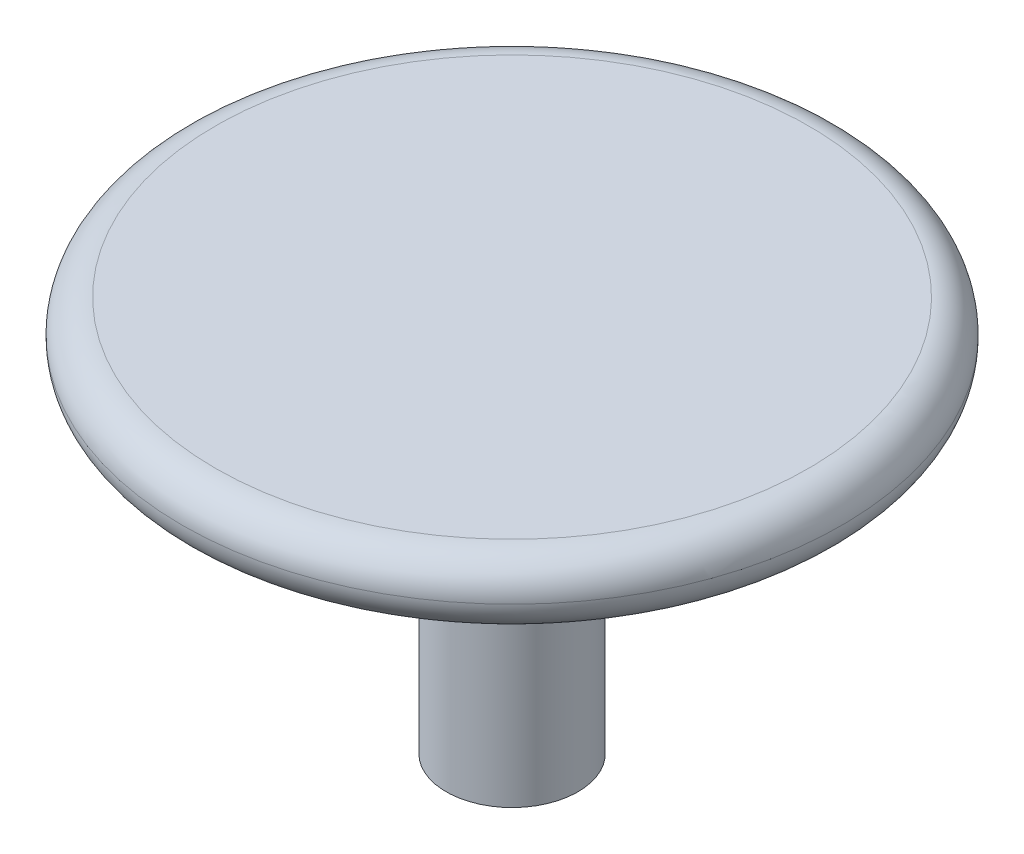
SolidWorks part; units mm, degrees
material "Silicon Rubber"
ref_plane "Front Plane" through (0, 0, 0) normal (0, 0, 1) x (1, 0, 0)
ref_plane "Top Plane" through (0, 0, 0) normal (0, 1, 0) x (1, 0, 0)
ref_plane "Right Plane" through (0, 0, 0) normal (1, 0, 0) x (0, 0, -1)
sketch "Sketch2" plane through (0, 0, 0) normal (0, 1, 0) x (1, 0, 0)
  circle A0 centre (0, 0) radius 2.5
  dimension "D1" = 5
extrude "Boss-Extrude1" add sketch "Sketch2" along normal blind 0.5 contours A0
sketch "Sketch3" plane through (0, 0, 0) normal (0, -1, 0) x (1, 0, 0)
  circle A0 centre (0, 0) radius 0.5
  dimension "D1" = 1
extrude "Boss-Extrude2" add sketch "Sketch3" along normal blind 2.5
fillet "Fillet1" radius 0.25 2 edges at (0, 0.5, 2.5) (0, 0, 2.5)
